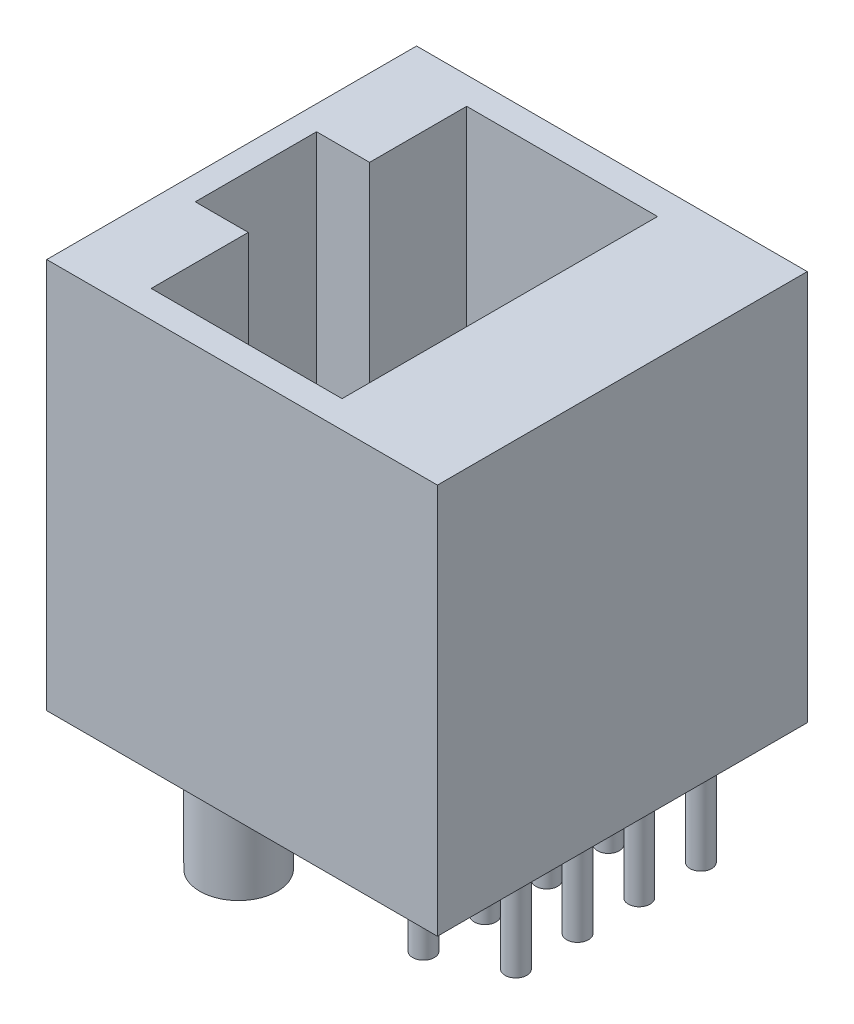
SolidWorks part; units mm, degrees
ref_plane "Front Plane" through (0, 0, 0) normal (0, 0, 1) x (1, 0, 0)
ref_plane "Top Plane" through (0, 0, 0) normal (0, 1, 0) x (1, 0, 0)
ref_plane "Right Plane" through (0, 0, 0) normal (1, 0, 0) x (0, 0, -1)
sketch "Sketch1" plane through (0, 0, 0) normal (0, 0, 1) x (1, 0, 0)
  line L1 (-8.05, -8.05) -> (8.05, -8.05)
  line L2 (-8.05, -8.05) -> (-8.05, 8.05)
  line L3 (-8.05, 8.05) -> (8.05, 8.05)
  line L4 (8.05, -8.05) -> (8.05, 8.05)
  line L5 (-8.05, -8.05) -> (8.05, 8.05) construction
  line L6 (-8.05, 8.05) -> (8.05, -8.05) construction
  point P0 (0, 0)
  dimension "D1" = 16.1
  dimension "D2" = 16.1
extrude "Boss-Extrude1" add sketch "Sketch1" along normal blind 15.24 contours L3 L4 L1 L2
fillet "Fillet1" [suppressed] radius 4
sketch "Sketch2" plane through (0, -8.05, 0) normal (0, -1, 0) x (1, 0, 0)
  line L0 (-8.05, 7.62) -> (8.05, 7.62) construction
  line L1 (-8.05, 15.24) -> (-8.05, 0) construction
  line L2 (8.05, 15.24) -> (8.05, 0) construction
  line L3 (-2.05, 1.905) -> (-2.05, 13.335) construction
  line L4 (6.84, 13.0064) -> (6.84, 2.2336) construction
  line L5 (4.3, 2.2336) -> (4.3, 13.0064) construction
  line L6 (5.316, 2.2336) -> (5.316, 13.0064) construction
  circle A0 centre (-2.05, 13.335) radius 1.6
  circle A1 centre (-2.05, 1.905) radius 1.6
  circle A2 centre (6.84, 8.255) radius 0.45
  circle A3 centre (4.3, 6.985) radius 0.45
  point P11 (-2.05, 7.62)
  point P15 (6.84, 7.62)
  point P16 (4.3, 7.62)
  dimension "D1" = 3.2
  dimension "D6" = 0.9
  dimension "D2" = 11.43
  dimension "D3" = 6
  dimension "D4" = 8.89
  dimension "D5" = 2.54
  dimension "D7" = 0.635
  dimension "D8" = 1.27
  dimension "D9" = 1.524
extrude "Boss-Extrude2" add sketch "Sketch2" along normal blind 3.6 contours A1 | A0 region at (-2.05, -8.05, 1.905)
extrude "Boss-Extrude3" add sketch "Sketch2<4>" along normal blind 4 contours A3 region at (4.3, -8.05, 6.985)
sketch "Sketch2<4>" plane through (0, -8.05, 0) normal (0, -1, 0) x (1, 0, 0) same geometry as "Sketch2"
extrude "Boss-Extrude4" add sketch "Sketch2<5>" along normal blind 4 contours A2
sketch "Sketch2<5>" plane through (0, -8.05, 0) normal (0, -1, 0) x (1, 0, 0) same geometry as "Sketch2"
pattern_linear "LPattern1" count 3 spacing 2.54 along (0, 0, -1) count 2 spacing 2.54 along (0, 0, 1) of "Boss-Extrude4"
pattern_linear "LPattern2" count 2 spacing 2.54 along (0, 0, -1) count 3 spacing 2.54 along (0, 0, 1) of "Boss-Extrude3"
sketch "Sketch3" plane through (0, 8.05, 0) normal (0, 1, 0) x (1, 0, 0)
  line L0 (-8.05, -15.24) -> (-8.05, 0) construction
  line L1 (3, -14.12) -> (-4.8657, -14.12)
  line L2 (3, -14.12) -> (3, -1.12)
  line L3 (3, -1.12) -> (-4.8657, -1.12)
  line L4 (-4.8657, -14.12) -> (-4.8657, -10.12)
  line L5 (-4.8657, -10.12) -> (-7.05, -10.12)
  line L6 (-7.05, -10.12) -> (-7.05, -5.12)
  line L7 (-7.05, -5.12) -> (-4.8657, -5.12)
  line L8 (-4.8657, -5.12) -> (-4.8657, -1.12)
  point P7 (-8.05, -7.62)
  point P13 (-7.05, -7.62)
  dimension "D1" = 13
  dimension "D2" = 3
  dimension "D3" = 1
  dimension "D4" = 5
extrude "Cut-Extrude1" cut sketch "Sketch3" against normal blind 10
